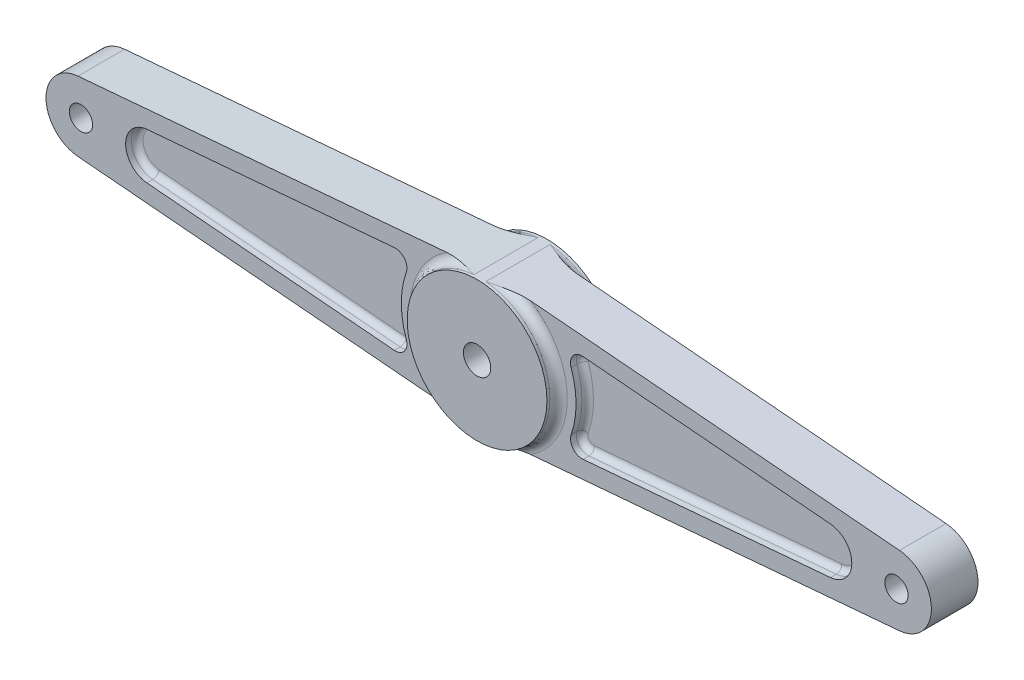
SolidWorks part; units mm, degrees
ref_plane "Front Plane" through (0, 0, 0) normal (0, 0, 1) x (1, 0, 0)
ref_plane "Top Plane" through (0, 0, 0) normal (0, 1, 0) x (1, 0, 0)
ref_plane "Right Plane" through (0, 0, 0) normal (1, 0, 0) x (0, 0, -1)
sketch "Sketch1" plane through (0, 0, 0) normal (0, 0, 1) x (1, 0, 0)
  line L0 (0, 93.7731) -> (0, -104.9985) construction
  line L1 (-70.5143, 5.9779) -> (-1.0286, 11.9558)
  line L2 (-70.5143, -5.9779) -> (-1.0286, -11.9558)
  line L3 (70.5143, 5.9779) -> (1.0286, 11.9558)
  line L4 (70.5143, -5.9779) -> (1.0286, -11.9558)
  arc A0 (-70.5143, 5.9779) -> (-70.5143, -5.9779) centre (-70, 0) ccw
  circle A1 centre (0, 0) radius 12
  circle A2 centre (-70, 0) radius 2
  circle A3 centre (70, 0) radius 2
  arc A4 (70.5143, 5.9779) -> (70.5143, -5.9779) centre (70, 0) cw
  dimension "D1" = 12
  dimension "D2" = 4
  dimension "D3" = 24
  dimension "D4" = 70
extrude "Boss-Extrude1" add sketch "Sketch1" along normal mid plane 8 contours A1 L1 A0 L2 A2 | A4 L3 A1 L4 A3 region at (-38.2625, 0, 0) region at (38.2625, 0, 0)
extrude "Boss-Extrude2" add sketch "Sketch1<3>" along normal mid plane 12 contours A1 L0 | L0 A1 region at (5.093, 0, 0) region at (-5.093, 0, 0)
sketch "Sketch1<3>" plane through (0, 0, 0) normal (0, 0, 1) x (1, 0, 0) same geometry as "Sketch1"
fillet "Fillet1" radius 1.5 4 edges at (-12, 0, -4) (12, 0, -4) (-12, 0, 4) (12, 0, 4)
sketch "Sketch2" plane through (0, 0, 6) normal (0, 0, 1) x (1, 0, 0)
  line L0 (87.241, 0) -> (-97.244, 0) construction
  circle A0 centre (0, 0) radius 2.3477
extrude "Cut-Extrude1" cut sketch "Sketch2" against normal through all
sketch "Sketch3" plane through (0, 0, 4) normal (0, 0, 1) x (1, 0, 0)
  line L2 (-70.2571, 2.989) -> (-6.9333, 8.4368)
  line L3 (-58.6762, 3.9853) -> (-16.2063, 7.639)
  line L10 (0, 45.1265) -> (0, -42.8005) construction
  line L11 (-70.2571, -2.989) -> (-6.9333, -8.4368)
  line L12 (-58.6762, -3.9853) -> (-16.2063, -7.639)
  line L13 (58.6762, -3.9853) -> (16.2063, -7.639)
  line L14 (58.6762, 3.9853) -> (16.2063, 7.639)
  arc A0 (-14.1485, 4.9821) -> (-14.1485, -4.9821) centre (0, 0) ccw
  arc A7 (-58.6762, 3.9853) -> (-58.6762, -3.9853) centre (-58.3333, 0) ccw
  arc A8 (-16.2063, -7.639) -> (-14.1485, -4.9821) centre (-16.0349, -5.6464) ccw
  arc A9 (-16.2063, 7.639) -> (-14.1485, 4.9821) centre (-16.0349, 5.6464) cw
  arc A10 (58.6762, 3.9853) -> (58.6762, -3.9853) centre (58.3333, 0) cw
  arc A11 (16.2063, -7.639) -> (14.1485, -4.9821) centre (16.0349, -5.6464) cw
  arc A12 (14.1485, 4.9821) -> (14.1485, -4.9821) centre (0, 0) cw
  arc A13 (16.2063, 7.639) -> (14.1485, 4.9821) centre (16.0349, 5.6464) ccw
  dimension "D1" = 30
  dimension "D4" = 8
  dimension "D5" = 2
  dimension "D2" = 3
  dimension "D3" = 3
extrude "Cut-Extrude2" cut sketch "Sketch3" against normal blind 2
sketch "Sketch4" plane through (0, 0, -4) normal (0, 0, -1) x (-1, 0, 0)
  line L2 (-16.2063, 7.639) -> (-58.6762, 3.9853)
  line L3 (-58.6762, -3.9853) -> (-16.2063, -7.639)
  line L4 (-16.2063, 7.639) -> (-58.6762, 3.9853)
  line L5 (-58.6762, -3.9853) -> (-16.2063, -7.639)
  line L6 (16.2063, -7.639) -> (58.6762, -3.9853)
  line L7 (58.6762, 3.9853) -> (16.2063, 7.639)
  line L8 (16.2063, -7.639) -> (58.6762, -3.9853)
  line L9 (58.6762, 3.9853) -> (16.2063, 7.639)
  arc A4 (-58.6762, 3.9853) -> (-58.6762, -3.9853) centre (-58.3333, 0) ccw
  arc A5 (-16.2063, -7.639) -> (-14.1485, -4.9821) centre (-16.0349, -5.6464) ccw
  arc A6 (-14.1485, 4.9821) -> (-14.1485, -4.9821) centre (0, 0) ccw
  arc A7 (-14.1485, 4.9821) -> (-16.2063, 7.639) centre (-16.0349, 5.6464) ccw
  arc A8 (-58.6762, 3.9853) -> (-58.6762, -3.9853) centre (-58.3333, 0) ccw
  arc A9 (-16.2063, -7.639) -> (-14.1485, -4.9821) centre (-16.0349, -5.6464) ccw
  arc A10 (-14.1485, 4.9821) -> (-14.1485, -4.9821) centre (0, 0) ccw
  arc A11 (-14.1485, 4.9821) -> (-16.2063, 7.639) centre (-16.0349, 5.6464) ccw
  arc A12 (16.2063, 7.639) -> (14.1485, 4.9821) centre (16.0349, 5.6464) ccw
  arc A13 (14.1485, -4.9821) -> (14.1485, 4.9821) centre (0, 0) ccw
  arc A14 (14.1485, -4.9821) -> (16.2063, -7.639) centre (16.0349, -5.6464) ccw
  arc A15 (58.6762, -3.9853) -> (58.6762, 3.9853) centre (58.3333, 0) ccw
  arc A16 (16.2063, 7.639) -> (14.1485, 4.9821) centre (16.0349, 5.6464) ccw
  arc A17 (14.1485, -4.9821) -> (14.1485, 4.9821) centre (0, 0) ccw
  arc A18 (14.1485, -4.9821) -> (16.2063, -7.639) centre (16.0349, -5.6464) ccw
  arc A19 (58.6762, -3.9853) -> (58.6762, 3.9853) centre (58.3333, 0) ccw
  dimension "D1" = 0
  dimension "D2" = 0
extrude "Cut-Extrude3" cut sketch "Sketch4" against normal blind 2
fillet "Fillet2" radius 1 12 edges at (-37.4413, 5.8121, -2) (-62.3333, 0, -2) (-37.4413, -5.8121, -2) (-14.4537, -6.871, -2) (-15, 0, -2) (-14.4537, 6.871, -2) (37.4413, 5.8121, -2) (14.4537, 6.871, -2) (15, 0, -2) (14.4537, -6.871, -2) (37.4413, -5.8121, -2) (62.3333, 0, -2)
fillet "Fillet3" radius 1 12 edges at (-37.4413, -5.8121, 2) (-62.3333, 0, 2) (-37.4413, 5.8121, 2) (-14.4537, 6.871, 2) (-15, 0, 2) (-14.4537, -6.871, 2) (37.4413, -5.8121, 2) (14.4537, -6.871, 2) (15, 0, 2) (14.4537, 6.871, 2) (37.4413, 5.8121, 2) (62.3333, 0, 2)
